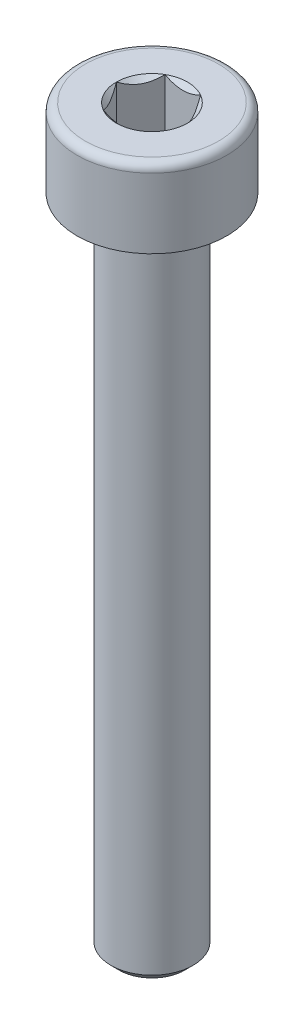
SolidWorks part; units mm, degrees
material "ASTM A36 Steel"
ref_plane "Front" through (0, 0, 0) normal (0, 0, 1) x (1, 0, 0)
ref_plane "Top" through (0, 0, 0) normal (0, 1, 0) x (1, 0, 0)
ref_plane "Right" through (0, 0, 0) normal (1, 0, 0) x (0, 0, -1)
sketch "Sketch1" plane through (0, 0, 0) normal (1, 0, 0) x (0, 0, -1)
  line L0 (0, 2.8377) -> (0, 0) construction
  line L1 (0, 0) -> (4.4824, 0) construction
  line L2 (0, -16) -> (0.8, -16)
  line L3 (0.8, -16) -> (1, -15.8)
  line L4 (1, -15.8) -> (1, -0.2)
  line L5 (1.2, 0) -> (1.825, 0)
  line L6 (1.825, 0) -> (1.825, 1.7)
  line L7 (1.625, 1.9) -> (0.8675, 1.9)
  line L8 (0, 0.1991) -> (0, -16)
  line L9 (0.75, 1.7825) -> (0.75, 0.9)
  line L10 (0.8675, 0.7) -> (0, 0.1991)
  line L11 (0.8675, 1.9) -> (0.75, 1.7825)
  line L12 (0.8675, 0.9) -> (0.8675, 0.7)
  line L13 (0.8675, 0.9) -> (0.75, 0.9)
  arc A0 (1, -0.2) -> (1.2, 0) centre (1.2, -0.2) cw
  arc A1 (1.825, 1.7) -> (1.625, 1.9) centre (1.625, 1.7) ccw
  dimension "D6" = 0.2
  dimension "D8" = 1.5
  dimension "D1" = 1.9
  dimension "D2" = 3.65
  dimension "D3" = 16
  dimension "D4" = 45
  dimension "D5" = 2
  dimension "D7" = 0.2
  dimension "D9" = 60
  dimension "D10" = 45
  dimension "D11" = 1.735
  dimension "D12" = 1
  dimension "D13" = 0.2
revolve "Revolve1" add sketch "Sketch1" angle 360 about L0
cosmetic thread "Cosmetic Thread1" parameters "D2"=1.548
sketch "Sketch2" plane through (0, 1.9, 0) normal (0, 1, 0) x (1, 0, 0)
  line L1 (0.433, -0.75) -> (0.866, 0)
  line L2 (0.866, 0) -> (0.433, 0.75)
  line L3 (0.433, 0.75) -> (-0.433, 0.75)
  line L4 (-0.433, 0.75) -> (-0.866, 0)
  line L5 (-0.866, 0) -> (-0.433, -0.75)
  line L6 (-0.433, -0.75) -> (0.433, -0.75)
  circle A0 centre (0, 0) radius 0.75 construction
  circle A1 centre (0, 0) radius 1.3095
  dimension "D1" = 1.5
extrude "Cut-Extrude1" cut sketch "Sketch2" against normal blind 1.1 contours L5 L6 L1 L2 L3 L4 region at (0, 1.9, 0)
extrude "Boss-Extrude1" add sketch "Sketch2<3>" against normal up to surface (0.4448 mm away) from offset 0.5 offset against normal yes
sketch "Sketch2<3>" plane through (0, 1.9, 0) normal (0, 1, 0) x (1, 0, 0) same geometry as "Sketch2"
